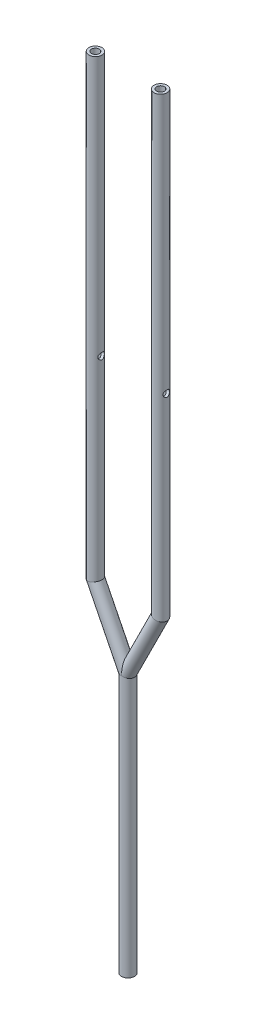
SolidWorks part; units mm, degrees
material "1060 Alloy"
ref_plane "Front Plane" through (0, 0, 0) normal (0, 0, 1) x (1, 0, 0)
ref_plane "Top Plane" through (0, 0, 0) normal (0, 1, 0) x (1, 0, 0)
ref_plane "Right Plane" through (0, 0, 0) normal (1, 0, 0) x (0, 0, -1)
sketch "Sketch2" plane through (0, 0, 0) normal (0, 0, 1) x (1, 0, 0)
  line L0 (0, 0) -> (-50, 0) construction
  line L1 (0, 0) -> (0, -800) construction
  line L2 (-50, 0) -> (-50, -700)
  line L3 (-50, -700) -> (0, -800)
  line L4 (0, -800) -> (0, -1200)
  dimension "D1" = 50
  dimension "D2" = 800
  dimension "D3" = 700
  dimension "D4" = 400
sweep "Sweep1" add path "Sketch2" circular profile diameter 20 parameters "D3"=20
sketch "Sketch7" plane through (0, 0, 0) normal (0, 0, 1) x (1, 0, 0)
  line L0 (0, 0) -> (50, 0) construction
  line L1 (0, 0) -> (0, -800) construction
  line L2 (50, 0) -> (50, -700)
  line L3 (50, -700) -> (0, -800)
  dimension "D1" = 800
  dimension "D2" = 50
  dimension "D3" = 700
sweep "Sweep2" add path "Sketch7" circular profile diameter 20 parameters "D3"=20
shell "Shell1" thickness 4 removed face at (-10, -1200, 0) removed face at (40, 0, 0) removed face at (-60, 0, 0)
sketch "Sketch14" plane through (0, 0, 0) normal (1, 0, 0) x (0, 0, -1)
  line L0 (0, 0) -> (0, -400) construction
  circle A0 centre (0, -400) radius 5
  dimension "D2" = 10
  dimension "D1" = 400
extrude "Cut-Extrude1" cut sketch "Sketch14" against normal through all both and the other way through all
